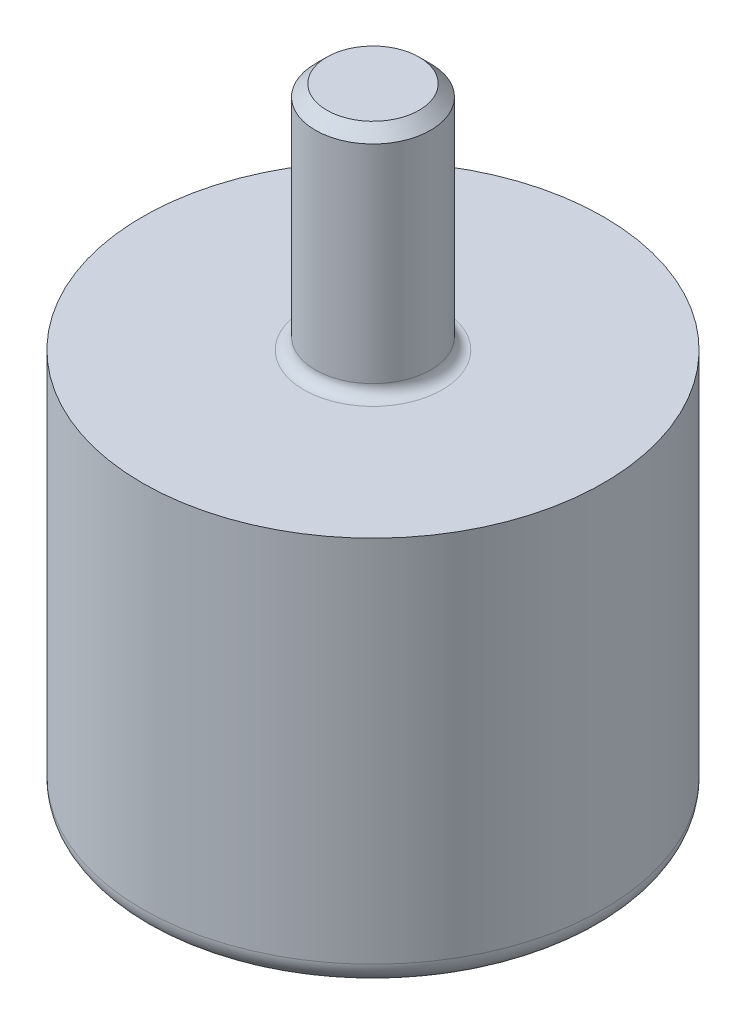
SolidWorks part; units mm, degrees
ref_plane "Face" through (0, 0, 0) normal (0, 0, 1) x (1, 0, 0)
ref_plane "Dessus" through (0, 0, 0) normal (0, 1, 0) x (1, 0, 0)
ref_plane "Droite" through (0, 0, 0) normal (1, 0, 0) x (0, 0, -1)
sketch "Esquisse1" plane through (0, 0, 0) normal (0, 0, 1) x (1, 0, 0)
  line L0 (0, 0) -> (0, 29.7645) construction
  line L1 (0, 17) -> (10, 17)
  line L2 (10, 17) -> (10, 0)
  line L3 (10, 0) -> (5.3385, 0)
  line L4 (0, 17) -> (0, 9.5)
  line L5 (0, 0) -> (0, -3) construction
  arc A0 (5.3385, 0) -> (0, 9.5) centre (0, 3.25) ccw
  dimension "D2" = 6.25
  dimension "D1" = 10
  dimension "D3" = 6.25
  dimension "D4" = 20
  dimension "D5" = 3
revolve "Révolution1" add sketch "Esquisse1" angle 360 about L0
sketch "Esquisse2" plane through (0, 17, 0) normal (0, 1, 0) x (1, 0, 0)
  circle A0 centre (0, 0) radius 2.5
  dimension "D1" = 5
extrude "Extrusion1" add sketch "Esquisse2" along normal blind 10
fillet "Congé1" radius 1 1 edges at (0, 0, -10)
chamfer "Chanfrein1" distance 0.5 angle 45 1 edges at (0, 27, 2.5)
fillet "Congé2" radius 0.5 1 edges at (0, 17, 2.5)
ref_axis "Axe1" through (0, 37.3309, 0) along (0, -1, 0)
